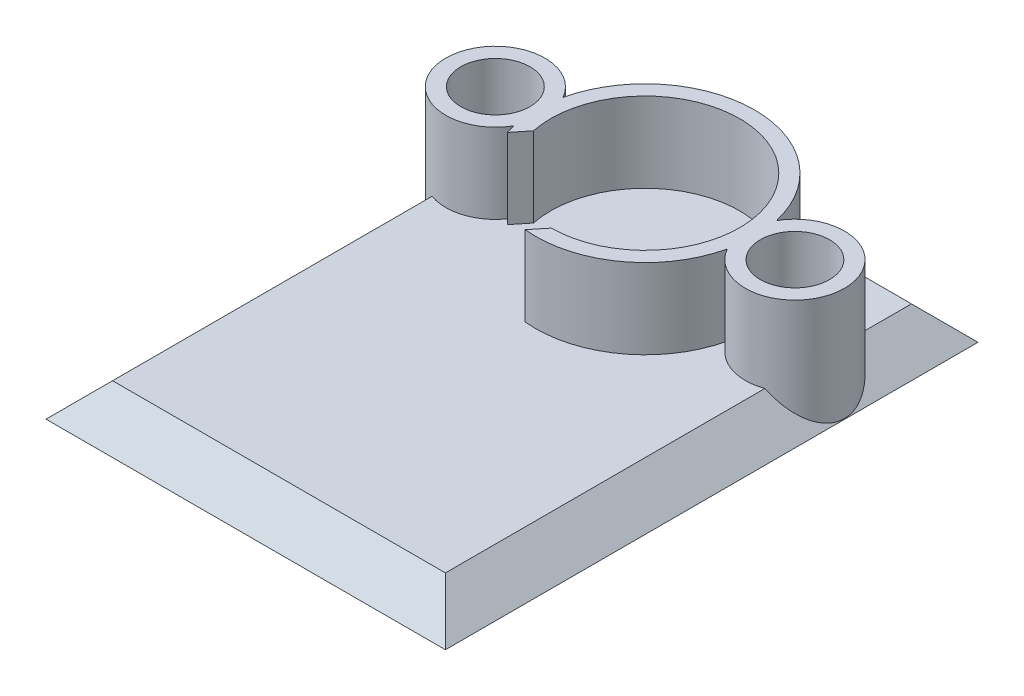
SolidWorks part; units mm, degrees
ref_plane "Front Plane" through (0, 0, 0) normal (0, 0, 1) x (1, 0, 0)
ref_plane "Top Plane" through (0, 0, 0) normal (0, 1, 0) x (1, 0, 0)
ref_plane "Right Plane" through (0, 0, 0) normal (1, 0, 0) x (0, 0, -1)
sketch "Sketch1" plane through (0, 0, 0) normal (0, 1, 0) x (1, 0, 0)
  line L0 (-22.5, 20) -> (22.5, 20) construction
  line L1 (-30, -40) -> (30, -40)
  line L2 (-30, -40) -> (-30, 40)
  line L3 (-30, 40) -> (30, 40)
  line L4 (30, -40) -> (30, 40)
  line L5 (-30, -40) -> (30, 40) construction
  line L6 (-30, 40) -> (30, -40) construction
  line L7 (0, 20) -> (0, 0) construction
  line L8 (-13.9045, 17.1181) -> (-15.6562, 14.9517)
  line L9 (-1.6595, 3.6339) -> (0.0922, 5.8003)
  line L10 (-14.7804, 16.0349) -> (-0.7837, 4.7171) construction
  line L11 (-7.782, 10.376) -> (0, 20)
  circle A0 centre (-22.5, 20) radius 5.2
  circle A1 centre (22.5, 20) radius 5.2
  circle A2 centre (0, 20) radius 14.2
  circle A3 centre (-22.5, 20) radius 7.45
  circle A4 centre (0, 20) radius 16.45
  circle A5 centre (22.5, 20) radius 7.45
  point P0 (0, 0)
  point P12 (0, 20)
  point P26 (-8.2427, 10.9903)
  dimension "D3" = 10.4
  dimension "D4" = 28.4
  dimension "D1" = 60
  dimension "D2" = 80
  dimension "D5" = 45
  dimension "D6" = 20
  dimension "D10" = 18
  dimension "D7" = 2.25
  dimension "D8" = 2.25
  dimension "D9" = 2.25
extrude "Boss-Extrude2" add sketch "Sketch1" against normal blind 5 contours L3 L4 L1 L2
extrude "Boss-Extrude4" add sketch "Sketch1<7>" along normal blind 12 contours A4 A3 A0 | A5 A4 A3 A2 | A3 A4 | A4 A5 A1 | A4 A5 region at (-15.1376, 0, -16.3238) region at (-15.8031, 0, -20) region at (-29.7461, 0, -20) region at (15.8031, 0, -20) region at (16.5473, 0, -18.1183)
sketch "Sketch1<7>" plane through (0, 0, 0) normal (0, 1, 0) x (1, 0, 0) same geometry as "Sketch1"
chamfer "Chamfer1" distance 5 angle 45 4 edges at (0, 0, -40) (30, 0, 0) (0, 0, 40) (-30, 0, 0)
